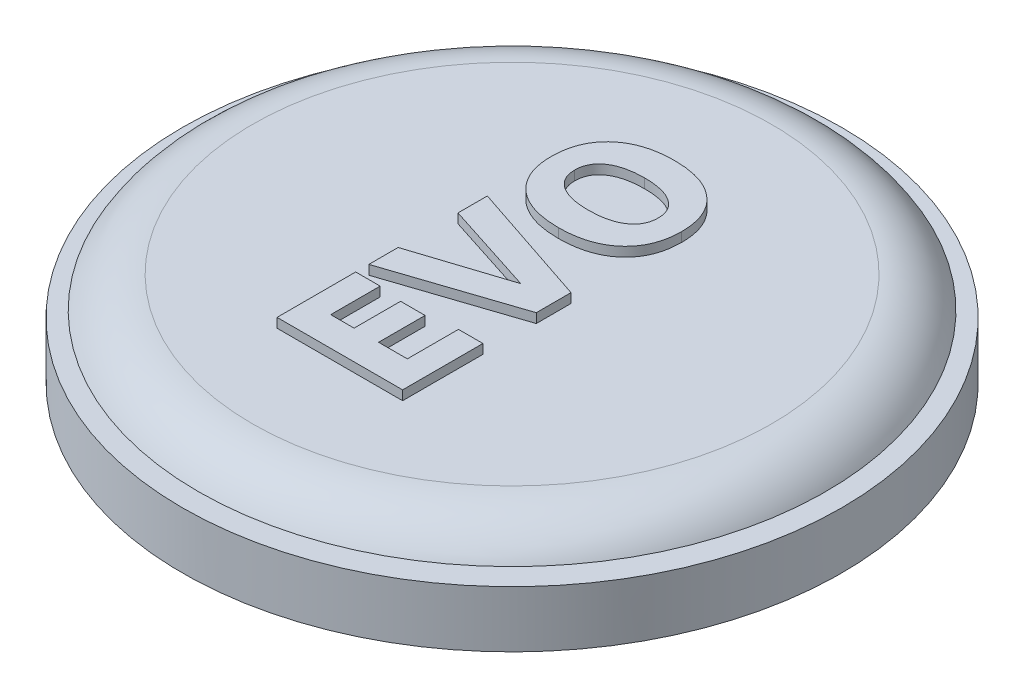
SolidWorks part; units mm, degrees
ref_plane "Спереди" through (0, 0, 0) normal (0, 0, 1) x (1, 0, 0)
ref_plane "Сверху" through (0, 0, 0) normal (0, 1, 0) x (1, 0, 0)
ref_plane "Справа" through (0, 0, 0) normal (1, 0, 0) x (0, 0, -1)
sketch "Sketch1" plane through (0, 0, 0) normal (0, 1, 0) x (1, 0, 0)
  circle A0 centre (0, 0) radius 17.35
  dimension "D1" = 34.7
extrude "Boss-Extrude1" add sketch "Sketch1" along normal blind 4
sketch "Sketch2" plane through (0, 4, 0) normal (0, 1, 0) x (1, 0, 0)
  circle A0 centre (0, 0) radius 20
  dimension "D1" = 40
extrude "Boss-Extrude2" add sketch "Sketch2" along normal blind 2
chamfer "Chamfer1" distance 0.5 angle 70 1 edges at (0, 0, 17.35) first distance on face at (0, 0, 17.35)
sketch "Sketch3" plane through (0, 6, 0) normal (0, 1, 0) x (1, 0, 0)
  line L0 (3.5, -19.6914) -> (3.5, 19.6914) construction
  line L1 (0, -20) -> (0, 20) construction
  circle A0 centre (0, 0) radius 20 construction
  text T0 "EVO" font "DejaVu Sans Condensed" height 8
  dimension "D1" = 3.5
extrude "Boss-Extrude3" add sketch "Sketch3" along normal blind 0.6
sketch "Sketch4" plane through (0, 0, 0) normal (0, -1, 0) x (1, 0, 0)
  circle A0 centre (0, 0) radius 17.85
  circle A1 centre (0, 0) radius 21
  circle A2 centre (0, 0) radius 16.85 construction
  circle A3 centre (0, 0) radius 20 construction
  dimension "D1" = 1
  dimension "D2" = 1
extrude "Boss-Extrude4" add sketch "Sketch4" against normal offset from surface (3.6 mm away) 0.4 separate body up to face at (0, 4, 17.35)
fillet "Fillet1" radius 4 1 edges at (0, 6, 20)
